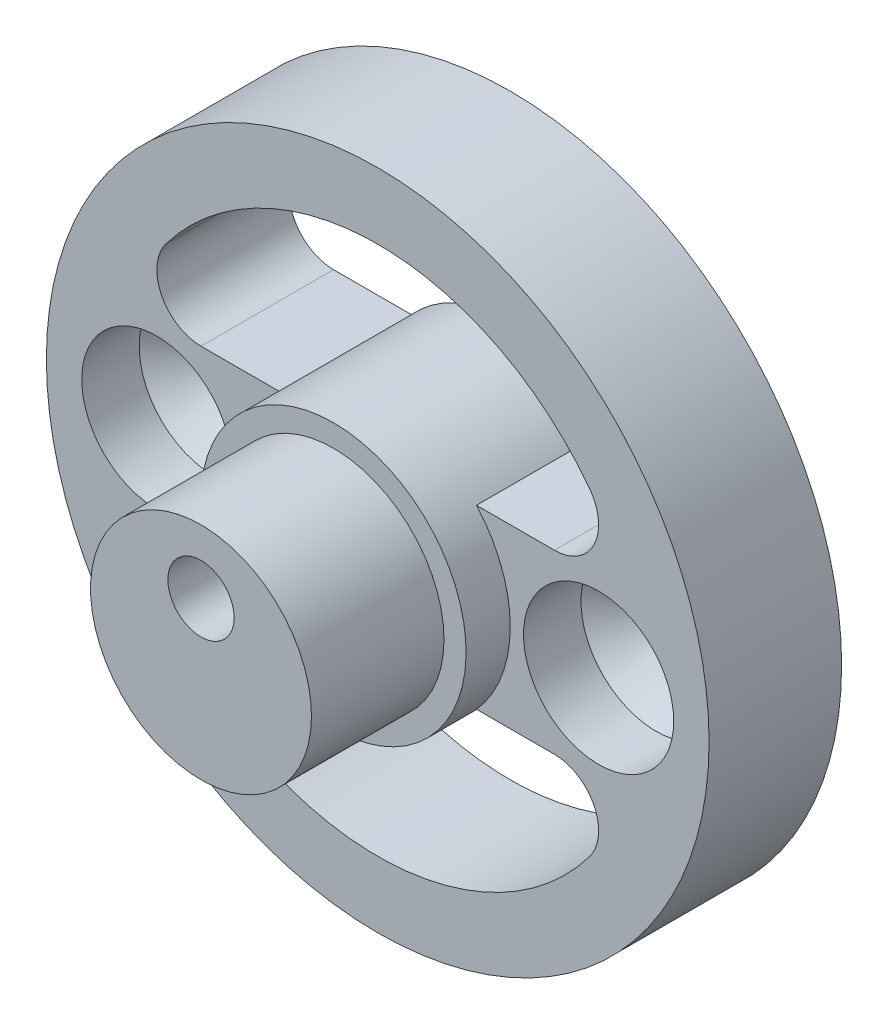
SolidWorks part; units mm, degrees
ref_plane "前视基准面" through (0, 0, 0) normal (0, 0, 1) x (1, 0, 0)
ref_plane "上视基准面" through (0, 0, 0) normal (0, 1, 0) x (1, 0, 0)
ref_plane "右视基准面" through (0, 0, 0) normal (1, 0, 0) x (0, 0, -1)
other "Configuration Table"
sketch "草图1" plane through (0, 0, 0) normal (0, 0, 1) x (1, 0, 0)
  circle A1 centre (0, 0) radius 5
  circle A2 centre (0, 1.051) radius 0.75
extrude "凸台-拉伸1" add sketch "草图1" along normal blind 3
sketch "草图3" plane through (0, 0, 3) normal (0, 0, 1) x (1, 0, 0)
  circle A0 centre (0, 0) radius 2.5
  circle A1 centre (0, 0) radius 6.373
extrude "切除-拉伸1" cut sketch "草图3" against normal blind 10
sketch "草图5" plane through (0, 0, 0) normal (0, 0, -1) x (-1, 0, 0)
  circle A0 centre (0, 0) radius 3
  circle A1 centre (0, 1.051) radius 0.75
extrude "凸台-拉伸3" add sketch "草图5" along normal blind 1
sketch "草图6" plane through (0, 0, -1) normal (0, 0, -1) x (-1, 0, 0)
  line L1 (2.2361, 2) -> (5.6569, 2)
  line L3 (2.2361, -2) -> (5.6569, -2)
  line L5 (-2.2361, -2) -> (-5.6569, -2)
  line L7 (-2.2361, 2) -> (-5.6569, 2)
  circle A1 centre (-5, 0) radius 1
  circle A2 centre (5, 0) radius 1
  circle A3 centre (0, 0) radius 7
  arc A4 (-5.6569, -2) -> (5.6569, -2) centre (0, 0) ccw
  arc A6 (5.6569, 2) -> (-5.6569, 2) centre (0, 0) ccw
  arc A7 (-2.2361, -2) -> (2.2361, -2) centre (0, 0) ccw
  arc A8 (2.2361, 2) -> (-2.2361, 2) centre (0, 0) ccw
  circle A9 centre (0, 1.051) radius 0.75
extrude "凸台-拉伸4" add sketch "草图6" along normal blind 3
fillet "圆角2" radius 1 4 edges at (5.6569, -2, -2.5) (5.6569, 2, -2.5) (-5.6569, 2, -2.5) (-5.6569, -2, -2.5)
sketch "草图7" plane through (0, 0, -1) normal (0, 0, 1) x (1, 0, 0)
  circle A0 centre (-5, 0) radius 1.5
  circle A1 centre (5, 0) radius 1.5
extrude "切除-拉伸2" cut sketch "草图7" against normal blind 2
chamfer "倒角1" distance 0.5 angle 45 2 edges at (6.5, 0, -3) (-3.5, 0, -3)
sketch "草图8" plane through (0, 0, -1) normal (0, 0, 1) x (1, 0, 0)
  circle A0 centre (-5, 0) radius 1.7
  circle A1 centre (5, 0) radius 1.7
extrude "切除-拉伸3" cut sketch "草图8" against normal blind 2
chamfer "倒角2" distance 0.7 angle 45 2 edges at (-3.3, 0, -3) (6.7, 0, -3)
sketch "草图9" plane through (0, 0, -1) normal (0, 0, 1) x (1, 0, 0)
  circle A0 centre (0, 0) radius 6.7
  circle A1 centre (0, 0) radius 7.5
extrude "凸台-拉伸5" add sketch "草图9" against normal blind 3
